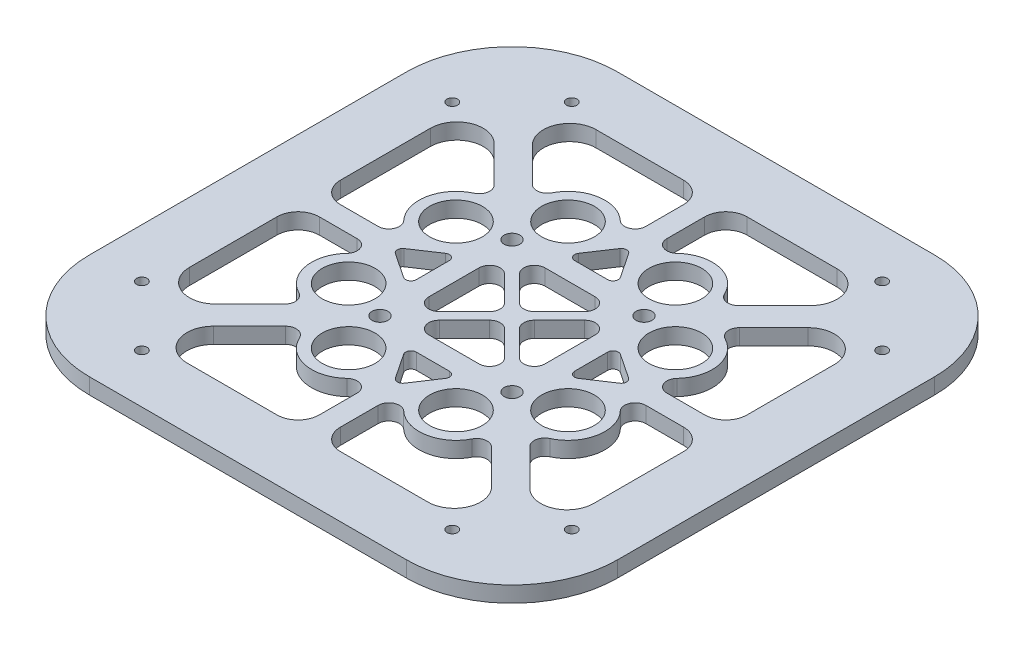
SolidWorks part; units mm, degrees
ref_plane "Plan de face" through (0, 0, 0) normal (0, 0, 1) x (1, 0, 0)
ref_plane "Plan de dessus" through (0, 0, 0) normal (0, 1, 0) x (1, 0, 0)
ref_plane "Plan de droite" through (0, 0, 0) normal (1, 0, 0) x (0, 0, -1)
sketch "Esquisse1" plane through (0, 0, 0) normal (0, 1, 0) x (1, 0, 0)
  line L0 (-50, 50) -> (50, -50) construction
  line L1 (-50, 50) -> (50, 50)
  line L2 (-50, 50) -> (-50, -50)
  line L3 (-50, -50) -> (50, -50)
  line L4 (50, 50) -> (50, -50)
  line L5 (50, 50) -> (-50, -50) construction
  line L6 (-12.5, 12.5) -> (12.5, 12.5) construction
  line L7 (12.5, 12.5) -> (12.5, -12.5) construction
  line L8 (12.5, -12.5) -> (-12.5, -12.5) construction
  line L9 (-15, 5) -> (-15, -5)
  line L10 (-40, -40) -> (40, -40) construction
  line L11 (40, -40) -> (40, 40) construction
  line L12 (40, 40) -> (-40, 40) construction
  line L13 (-40, 40) -> (-40, -40) construction
  line L14 (-5, -15) -> (5, -15)
  line L15 (5, -15) -> (0, -22.5)
  line L16 (0, -22.5) -> (-5, -15)
  line L17 (0, -22.5) -> (0, -40) construction
  line L18 (0, -1.4142) -> (-9.5858, -11)
  line L19 (-9.5858, -11) -> (9.5858, -11)
  line L20 (9.5858, -11) -> (0, -1.4142)
  line L21 (-35.1213, -38.5) -> (-13.9031, -17.2818) construction
  line L22 (-35.1213, -38.5) -> (-2, -38.5)
  line L23 (-2, -38.5) -> (-2, -21)
  line L24 (2, -38.5) -> (2, -21)
  line L25 (34.635, -38.5) -> (2, -38.5)
  line L26 (34.635, -38.5) -> (13.4218, -17.2868) construction
  line L27 (-17.1618, -20.5406) -> (-35.1213, -38.5)
  line L28 (-15, -5) -> (-22.5, 0)
  line L29 (-22.5, 0) -> (-15, 5)
  line L30 (-1.4142, 0) -> (-11, 9.5858)
  line L31 (-11, 9.5858) -> (-11, -9.5858)
  line L32 (-11, -9.5858) -> (-1.4142, 0)
  line L33 (-38.5, 35.1213) -> (-38.5, 2)
  line L34 (-38.5, 2) -> (-21, 2)
  line L35 (-38.5, -2) -> (-21, -2)
  line L36 (-38.5, -34.635) -> (-38.5, -2)
  line L37 (-20.5406, 17.1618) -> (-38.5, 35.1213)
  line L38 (-21.0261, -17.1611) -> (-38.5, -34.635)
  line L39 (-21, 2) -> (-24.5463, 4.2702)
  line L40 (-12.5, -12.5) -> (-12.5, 12.5) construction
  line L41 (-21, -2) -> (-24.5463, -4.2702)
  line L42 (-22.5, 0) -> (-40, 0) construction
  line L43 (-38.5, 35.1213) -> (-17.2818, 13.9031) construction
  line L44 (-38.5, -34.635) -> (-17.2868, -13.4218) construction
  line L45 (0, 1.4142) -> (9.5858, 11)
  line L46 (9.5858, 11) -> (-9.5858, 11)
  line L47 (-9.5858, 11) -> (0, 1.4142)
  line L48 (5, 15) -> (-5, 15)
  line L49 (-5, 15) -> (0, 22.5)
  line L50 (0, 22.5) -> (5, 15)
  line L51 (35.1213, 38.5) -> (2, 38.5)
  line L52 (2, 38.5) -> (2, 21)
  line L53 (-2, 38.5) -> (-2, 21)
  line L54 (-34.635, 38.5) -> (-2, 38.5)
  line L55 (-12.5, 12.5) -> (12.5, 12.5) construction
  line L56 (17.1618, 20.5406) -> (35.1213, 38.5)
  line L57 (-17.1611, 21.0261) -> (-34.635, 38.5)
  line L58 (2, 21) -> (4.2702, 24.5463)
  line L59 (-2, 21) -> (-4.2702, 24.5463)
  line L60 (1.4142, 0) -> (11, -9.5858)
  line L61 (11, -9.5858) -> (11, 9.5858)
  line L62 (11, 9.5858) -> (1.4142, 0)
  line L63 (0, 22.5) -> (0, 40) construction
  line L64 (35.1213, 38.5) -> (13.9031, 17.2818) construction
  line L65 (-34.635, 38.5) -> (-13.4218, 17.2868) construction
  line L66 (15, -5) -> (15, 5)
  line L67 (15, 5) -> (22.5, 0)
  line L68 (22.5, 0) -> (15, -5)
  line L69 (38.5, -35.1213) -> (38.5, -2)
  line L70 (12.5, 12.5) -> (12.5, -12.5) construction
  line L71 (38.5, -2) -> (21, -2)
  line L72 (38.5, 2) -> (21, 2)
  line L73 (28.9675, -41.133) -> (41.6954, -28.4051) construction
  line L74 (-41.133, -28.9675) -> (-28.4051, -41.6954) construction
  line L75 (-28.9675, 41.133) -> (-41.6954, 28.4051) construction
  line L76 (41.133, 28.9675) -> (28.4051, 41.6954) construction
  line L82 (17.1611, -21.0261) -> (34.635, -38.5)
  line L83 (-2, -21) -> (-4.2702, -24.5463)
  line L84 (2, -21) -> (4.2702, -24.5463)
  line L85 (38.5, 34.635) -> (38.5, 2)
  line L86 (20.5406, -17.1618) -> (38.5, -35.1213)
  line L87 (21.0261, 17.1611) -> (38.5, 34.635)
  line L88 (21, -2) -> (24.5463, -4.2702)
  line L89 (21, 2) -> (24.5463, 4.2702)
  line L90 (22.5, 0) -> (40, 0) construction
  line L91 (38.5, -35.1213) -> (17.2818, -13.9031) construction
  line L92 (38.5, 34.635) -> (17.2868, 13.4218) construction
  circle A0 centre (-10.1657, -20.7723) radius 5
  circle A1 centre (10.1657, -20.7723) radius 5
  arc A2 (-4.2702, -24.5463) -> (-17.1618, -20.5406) centre (-10.1657, -20.7723) cw
  arc A3 (4.2702, -24.5463) -> (17.1611, -21.0261) centre (10.1657, -20.7723) ccw
  circle A4 centre (-20.7723, 10.1657) radius 5
  circle A5 centre (-20.7723, -10.1657) radius 5
  arc A6 (-24.5463, 4.2702) -> (-20.5406, 17.1618) centre (-20.7723, 10.1657) cw
  arc A7 (-24.5463, -4.2702) -> (-21.0261, -17.1611) centre (-20.7723, -10.1657) ccw
  circle A8 centre (10.1657, 20.7723) radius 5
  circle A9 centre (-10.1657, 20.7723) radius 5
  arc A10 (4.2702, 24.5463) -> (17.1618, 20.5406) centre (10.1657, 20.7723) cw
  arc A11 (-4.2702, 24.5463) -> (-17.1611, 21.0261) centre (-10.1657, 20.7723) ccw
  circle A12 centre (20.7723, -10.1657) radius 5
  circle A13 centre (20.7723, 10.1657) radius 5
  arc A14 (24.5463, -4.2702) -> (20.5406, -17.1618) centre (20.7723, -10.1657) cw
  arc A15 (24.5463, 4.2702) -> (21.0261, 17.1611) centre (20.7723, 10.1657) ccw
  circle A16 centre (-12.5, -12.5) radius 1.5
  circle A17 centre (12.5, -12.5) radius 1.5
  circle A18 centre (12.5, 12.5) radius 1.5
  circle A19 centre (-12.5, 12.5) radius 1.5
  circle A20 centre (29.3934, -40.7071) radius 1
  circle A21 centre (40.7071, -29.3934) radius 1
  circle A22 centre (-40.7071, -29.3934) radius 1
  circle A23 centre (-29.3934, -40.7071) radius 1
  circle A24 centre (-29.3934, 40.7071) radius 1
  circle A25 centre (-40.7071, 29.3934) radius 1
  circle A26 centre (40.7071, 29.3934) radius 1
  circle A27 centre (29.3934, 40.7071) radius 1
  dimension "D11" = 10
  dimension "D13" = 10
  dimension "D25" = 7
  dimension "D26" = 7
  dimension "D28" = 7
  dimension "D29" = 8
  dimension "D1" = 1.5
  dimension "D2" = 100
  dimension "D3" = 10
  dimension "D4" = 100
  dimension "D5" = 50
  dimension "D6" = 50
  dimension "D7" = 1
  dimension "D8" = 25
  dimension "D9" = 2.5
  dimension "D10" = 7.5
  dimension "D12" = 1.5
  dimension "D14" = 7.5
  dimension "D15" = 7.5
  dimension "D16" = 7.5
  dimension "D17" = 10
  dimension "D18" = 7.5
  dimension "D19" = 5
  dimension "D20" = 2
  dimension "D21" = 2
  dimension "D22" = 1.5
  dimension "D23" = 17.5
  dimension "D24" = 17.5
  dimension "D30" = 8
  dimension "D31" = 18
  dimension "D32" = 4
  dimension "D27" = 4
extrude "Boss.-Extru.1" add sketch "Esquisse1" along normal blind 3
fillet "Congé1" radius 20 4 edges at (-50, 1.5, -50) (50, 1.5, -50) (50, 1.5, 50) (-50, 1.5, 50)
fillet "Congé2" radius 5 8 edges at (34.635, 1.5, 38.5) (38.5, 1.5, 35.1213) (38.5, 1.5, -34.635) (35.1213, 1.5, -38.5) (-38.5, 1.5, -35.1213) (-34.635, 1.5, -38.5) (-38.5, 1.5, 34.635) (-35.1213, 1.5, 38.5)
fillet "Congé3" radius 4 8 edges at (38.5, 1.5, -2) (38.5, 1.5, 2) (2, 1.5, 38.5) (-2, 1.5, 38.5) (-38.5, 1.5, 2) (-38.5, 1.5, -2) (2, 1.5, -38.5) (-2, 1.5, -38.5)
fillet "Congé4" radius 2 28 edges at (9.5858, 1.5, 11) (-9.5858, 1.5, 11) (11, 1.5, 9.5858) (9.5858, 1.5, -11) (11, 1.5, -9.5858) (1.4142, 1.5, 0) (-9.5858, 1.5, -11) (0, 1.5, 1.4142) (-11, 1.5, 9.5858) (-1.4142, 1.5, 0) (-11, 1.5, -9.5858) (0, 1.5, -1.4142) (-17.1611, 1.5, -21.0261) (-2, 1.5, -21) (2, 1.5, -21) (17.1618, 1.5, -20.5406) (21.0261, 1.5, -17.1611) (21, 1.5, -2) (21, 1.5, 2) (-21, 1.5, -2) (-21, 1.5, 2) (-21.0261, 1.5, 17.1611) (-17.1618, 1.5, 20.5406) (-2, 1.5, 21) (2, 1.5, 21) (17.1611, 1.5, 21.0261) (20.5406, 1.5, 17.1618) (-20.5406, 1.5, -17.1618)
fillet "Congé5" radius 1 12 edges at (15, 1.5, -5) (0, 1.5, -22.5) (-15, 1.5, -5) (5, 1.5, 15) (22.5, 1.5, 0) (5, 1.5, -15) (-15, 1.5, 5) (0, 1.5, 22.5) (15, 1.5, 5) (-5, 1.5, -15) (-22.5, 1.5, 0) (-5, 1.5, 15)
ref_axis "Axe1" through (0, 3.15, 0) along (0, -1, 0)
